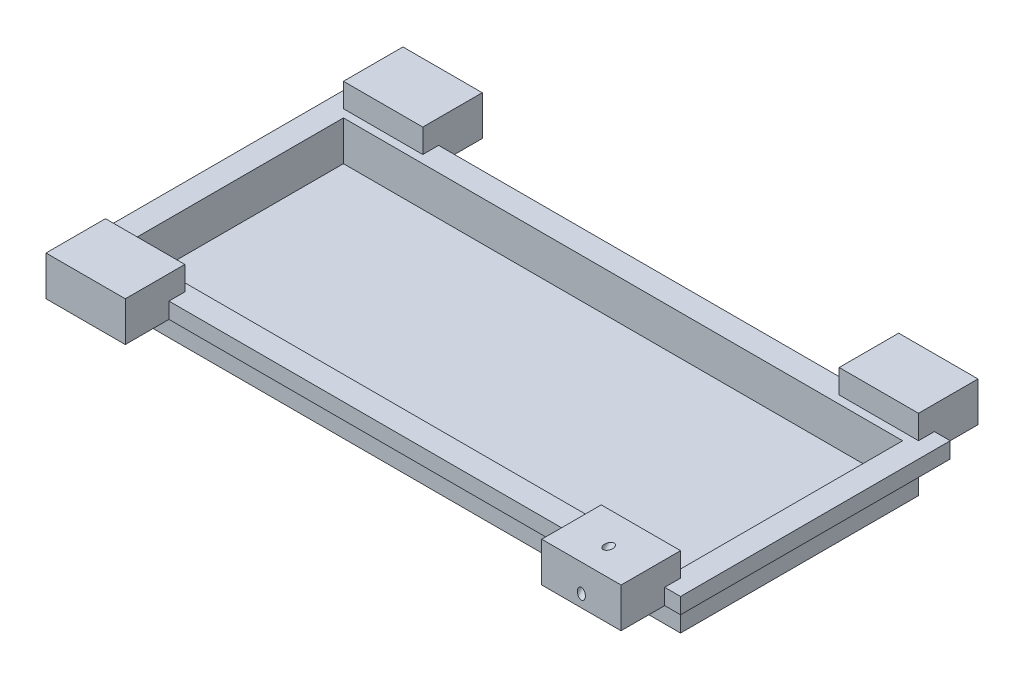
SolidWorks part; units mm, degrees
ref_plane "Front Plane" through (0, 0, 0) normal (0, 0, 1) x (1, 0, 0)
ref_plane "Top Plane" through (0, 0, 0) normal (0, 1, 0) x (1, 0, 0)
ref_plane "Right Plane" through (0, 0, 0) normal (1, 0, 0) x (0, 0, -1)
sketch "Sketch1" plane through (0, 0, 0) normal (0, 1, 0) x (1, 0, 0)
  line L0 (0, 0) -> (-72.5, 0) construction
  line L1 (-72.5, 30) -> (72.5, 30)
  line L2 (-72.5, 30) -> (-72.5, -30)
  line L3 (-72.5, -30) -> (72.5, -30)
  line L4 (72.5, 30) -> (72.5, -30)
  line L5 (0, 0) -> (0, 30) construction
  line L6 (-70.5, 28) -> (-70.5, -28)
  line L7 (-70.5, -28) -> (70.5, -28)
  line L8 (70.5, 28) -> (70.5, -28)
  line L9 (-70.5, 28) -> (70.5, 28)
  dimension "D1" = 145
  dimension "D2" = 60
  dimension "D3" = 2
extrude "Boss-Extrude1" add sketch "Sketch1" along normal blind 10
sketch "Sketch2" plane through (0, 0, 0) normal (0, -1, 0) x (1, 0, 0)
  line L4 (-72.5, 30) -> (-72.5, -30)
  line L5 (-72.5, -30) -> (72.5, -30)
  line L6 (72.5, -30) -> (72.5, 30)
  line L7 (72.5, 30) -> (-72.5, 30)
  line L8 (-72.5, 30) -> (-72.5, -30)
  line L9 (-72.5, -30) -> (72.5, -30)
  line L10 (72.5, -30) -> (72.5, 30)
  line L11 (72.5, 30) -> (-72.5, 30)
  dimension "D1" = 0
extrude "Boss-Extrude2" add sketch "Sketch2" along normal blind 2
sketch "Sketch3" plane through (0, 10, 0) normal (0, 1, 0) x (1, 0, 0)
  line L4 (72.5, -30) -> (72.5, 30) construction
  line L5 (-72.5, -30) -> (72.5, -30) construction
  line L6 (-72.5, 30) -> (-72.5, -30) construction
  line L7 (72.5, 30) -> (-72.5, 30) construction
  line L8 (-76.5, 34) -> (-76.5, -34)
  line L9 (-76.5, -34) -> (76.5, -34)
  line L10 (76.5, -34) -> (76.5, 34)
  line L11 (76.5, 34) -> (-76.5, 34)
  line L12 (-76.5, 34) -> (-76.5, -34)
  line L13 (-76.5, -34) -> (76.5, -34)
  line L14 (76.5, -34) -> (76.5, 34)
  line L15 (76.5, 34) -> (-76.5, 34)
  line L16 (72.5, -30) -> (72.5, 30)
  line L17 (-72.5, -30) -> (72.5, -30)
  line L18 (-72.5, 30) -> (-72.5, -30)
  line L19 (72.5, 30) -> (-72.5, 30)
  dimension "D1" = 4
extrude "Boss-Extrude3" add sketch "Sketch3" against normal blind 4
chamfer "Chamfer1" distance 4 angle 45 4 edges at (0, 6, -30) (72.5, 6, 0) (0, 6, 30) (-72.5, 6, 0)
sketch "Sketch4" plane through (0, 10, 0) normal (0, 1, 0) x (1, 0, 0)
  line L0 (0, 0) -> (0, 58.9321) construction
  line L1 (-72.5, 30) -> (-52.5, 30)
  line L2 (-72.5, 30) -> (-72.5, 45)
  line L3 (-72.5, 45) -> (-52.5, 45)
  line L4 (-72.5, -30) -> (72.5, -30)
  line L5 (-72.5, 30) -> (-72.5, -30)
  line L6 (72.5, 30) -> (-72.5, 30)
  line L7 (72.5, -30) -> (72.5, 30)
  line L8 (-72.5, -30) -> (72.5, -30) construction
  line L9 (-72.5, 30) -> (-72.5, -30) construction
  line L10 (72.5, 30) -> (-72.5, 30) construction
  line L11 (72.5, -30) -> (72.5, 30) construction
  line L12 (-52.5, 30) -> (-52.5, 45)
  line L13 (0, 0) -> (33.1222, 0) construction
  line L14 (-72.5, -45) -> (-52.5, -45)
  line L15 (-52.5, -30) -> (-52.5, -45)
  line L16 (-72.5, -30) -> (-52.5, -30)
  line L17 (-72.5, -30) -> (-72.5, -45)
  line L18 (72.5, -30) -> (72.5, -45)
  line L19 (72.5, -30) -> (52.5, -30)
  line L20 (52.5, -30) -> (52.5, -45)
  line L21 (72.5, -45) -> (52.5, -45)
  line L22 (72.5, 45) -> (52.5, 45)
  line L23 (52.5, 30) -> (52.5, 45)
  line L24 (72.5, 30) -> (52.5, 30)
  line L25 (72.5, 30) -> (72.5, 45)
  line L26 (-62.5, 37.5) -> (-72.5, 37.5) construction
  line L27 (-62.5, 45) -> (-62.5, 37.5) construction
  circle A0 centre (-62.5, 37.5) radius 1 construction
  circle A1 centre (-62.5, -37.5) radius 1 construction
  circle A2 centre (62.5, 37.5) radius 1 construction
  circle A3 centre (62.5, -37.5) radius 1 construction
  point P26 (0, 0)
  dimension "D4" = 2
  dimension "D2" = 20
  dimension "D3" = 15
  dimension "D1" = 0
extrude "Boss-Extrude4" add sketch "Sketch4" along normal blind 10 from vertex starting at point (-76.5, 6, -34)
ref_plane "Plane2" through (0, -14.5, 14.5) normal (0, 0.7071, -0.7071) x (1, 0, 0)
sketch "Sketch6" plane through (0, -14.5, 14.5) normal (0, 0.7071, -0.7071) x (1, 0, 0)
  line L0 (62.5, -43.1335) -> (62.5, -38.2619) construction
  line L1 (52.5, -43.1335) -> (72.5, -43.1335) construction
  circle A0 centre (62.5, -38.2619) radius 1
  dimension "D1" = 2
extrude "Cut-Extrude2" cut sketch "Sketch6" against normal through all and the other way through all
